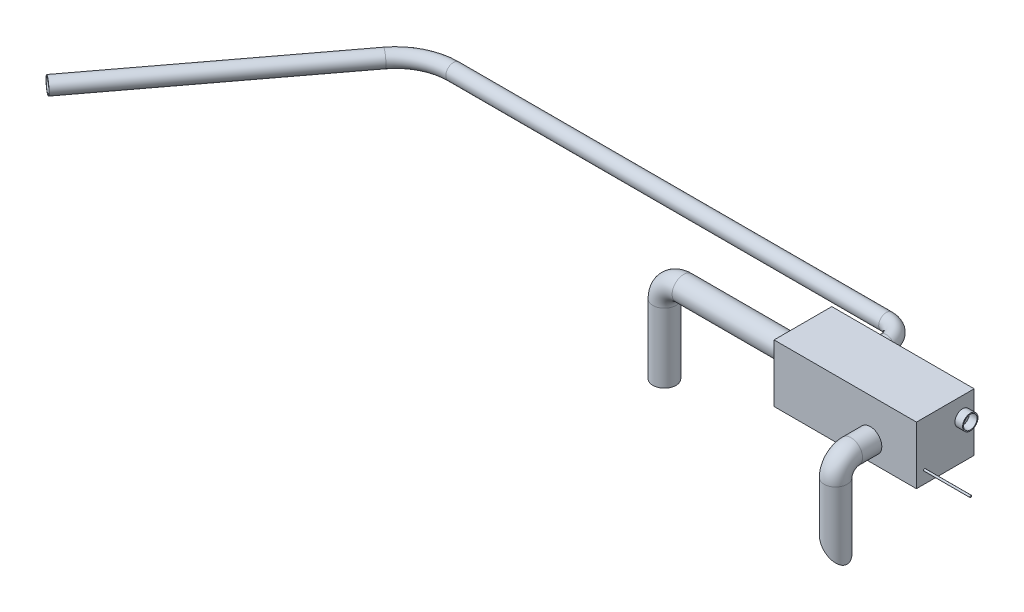
SolidWorks part; units mm, degrees
ref_plane "Front" through (0, 0, 0) normal (0, 0, 1) x (1, 0, 0)
ref_plane "Top" through (0, 0, 0) normal (0, 1, 0) x (1, 0, 0)
ref_plane "Right" through (0, 0, 0) normal (1, 0, 0) x (0, 0, -1)
sketch "Sketch1" plane through (0, 0, 0) normal (0, 1, 0) x (1, 0, 0)
  line L1 (-469.9, 190.5) -> (469.9, 190.5)
  line L2 (-469.9, 190.5) -> (-469.9, -190.5)
  line L3 (-469.9, -190.5) -> (469.9, -190.5)
  line L4 (469.9, 190.5) -> (469.9, -190.5)
  line L5 (-469.9, 190.5) -> (469.9, -190.5) construction
  line L6 (-469.9, -190.5) -> (469.9, 190.5) construction
  point P0 (0, 0)
  dimension "D1" = 381
  dimension "D2" = 939.8
extrude "Boss-Extrude1" add sketch "Sketch1" along normal blind 381
sketch "Sketch2" plane through (0, 0, 190.5) normal (0, 0, 1) x (1, 0, 0)
  line L0 (469.9, 381) -> (469.9, 0) construction
  line L1 (-469.9, 381) -> (469.9, 381) construction
  circle A0 centre (165.1, 127) radius 76.2
  circle A1 centre (165.1, 127) radius 69.85
  dimension "D1" = 152.4
  dimension "D3" = 254
  dimension "D4" = 139.7
  dimension "D2" = 304.8
extrude "Boss-Extrude2" add sketch "Sketch2" along normal blind 101.6
sketch "Sketch3" plane through (469.9, 0, 0) normal (1, 0, 0) x (0, 0, -1)
  line L0 (-190.5, 381) -> (190.5, 381) construction
  line L1 (190.5, 381) -> (190.5, 0) construction
  circle A0 centre (114.3, 254) radius 50.8
  circle A1 centre (114.3, 254) radius 44.45
  dimension "D1" = 101.6
  dimension "D2" = 88.9
  dimension "D3" = 127
  dimension "D4" = 76.2
extrude "Boss-Extrude3" add sketch "Sketch3" along normal blind 50.8
sketch "Sketch4" plane through (469.9, 0, 0) normal (1, 0, 0) x (0, 0, -1)
  circle A0 centre (-136.8501, 81.3511) radius 6.35
  dimension "D1" = 12.7
extrude "Boss-Extrude4" add sketch "Sketch4" along normal blind 304.8
sketch "Sketch5" plane through (0, 0, -190.5) normal (0, 0, -1) x (-1, 0, 0)
  line L0 (-469.9, 381) -> (469.9, 381) construction
  line L1 (469.9, 381) -> (469.9, 0) construction
  circle A0 centre (185.6926, 273.8882) radius 50.8
  circle A1 centre (185.6926, 273.8882) radius 44.45
  dimension "D1" = 101.6
  dimension "D2" = 88.9
  dimension "D4" = 284.2074
  dimension "D3" = 107.1118
extrude "Boss-Extrude5" add sketch "Sketch5" along normal blind 50.8
sketch "Sketch6" plane through (-469.9, 0, 0) normal (-1, 0, 0) x (0, 0, 1)
  line L0 (-190.5, 381) -> (190.5, 0) construction
  circle A0 centre (0, 190.5) radius 76.2
  circle A1 centre (0, 190.5) radius 69.85
  dimension "D1" = 152.4
  dimension "D2" = 139.7
extrude "Boss-Extrude6" add sketch "Sketch6" along normal blind 762
sketch "Sketch7" plane through (0, 0, 292.1) normal (0, 0, 1) x (1, 0, 0)
  circle A0 centre (165.1, 127) radius 76.2 construction
  circle A1 centre (165.1, 127) radius 76.2
  circle A2 centre (165.1, 127) radius 69.85 construction
  circle A3 centre (165.1, 127) radius 69.85
ref_point "Point1"
ref_plane "Plane1" through (165.1, 0, 0) normal (1, 0, 0) x (0, 0, -1)
sketch "Sketch8" plane through (165.1, 0, 0) normal (1, 0, 0) x (0, 0, -1)
  line L0 (-292.1, 127) -> (-317.5, 127)
  line L1 (-292.1, 203.2) -> (-292.1, 50.8) construction
  line L2 (-419.1, 25.4) -> (-419.1, -431.8)
  arc A0 (-317.5, 127) -> (-419.1, 25.4) centre (-317.5, 25.4) ccw
  dimension "D3" = 101.6
  dimension "D1" = 457.2
  dimension "D2" = 25.4
sweep "Sweep1" add profiles "Sketch7" path "Sketch8"
ref_point "Point2"
ref_plane "Plane2" through (0, 190.5, 0) normal (0, 1, 0) x (1, 0, 0)
sketch "Sketch9" plane through (0, 190.5, 0) normal (0, 1, 0) x (1, 0, 0)
  line L0 (-1231.9, 0) -> (-4279.9, 0)
  line L1 (-1231.9, 76.2) -> (-1231.9, -76.2) construction
  dimension "D1" = 3048
sketch "Sketch10" plane through (-1231.9, 0, 0) normal (-1, 0, 0) x (0, 0, 1)
  circle A0 centre (0, 190.5) radius 76.2 construction
  circle A1 centre (0, 190.5) radius 76.2
  circle A2 centre (0, 190.5) radius 69.85 construction
  circle A3 centre (0, 190.5) radius 69.85
sweep "Sweep2" [suppressed] add profiles "Sketch10" path "Sketch9"
ref_point "Point5"
ref_plane "Plane5" through (0, 273.8882, 0) normal (0, 1, 0) x (1, 0, 0)
sketch "Sketch13" plane through (0, 273.8882, 0) normal (0, 1, 0) x (1, 0, 0)
  line L0 (-185.6926, 241.3) -> (-185.6926, 266.7)
  line L1 (-134.8926, 241.3) -> (-236.4926, 241.3) construction
  line L2 (-181.0972, 292.7619) -> (330.9506, 1699.6019)
  line L3 (340.1415, 1751.7257) -> (340.1415, 2867.8535)
  line L4 (469.9, 190.5) -> (-469.9, 190.5) construction
  arc A0 (-185.6926, 266.7) -> (-181.0972, 292.7619) centre (-109.4926, 266.7) cw
  arc A1 (340.1415, 1751.7257) -> (330.9506, 1699.6019) centre (187.7415, 1751.7257) cw
  point P13 (340.1415, 1724.8535)
  dimension "D1" = 76.2
  dimension "D6" = 152.4
  dimension "D2" = 25.4
  dimension "D3" = 1524
  dimension "D4" = 1143
  dimension "D5" = 70
sketch "Sketch14" plane through (0, 0, -241.3) normal (0, 0, -1) x (-1, 0, 0)
  circle A0 centre (185.6926, 273.8882) radius 44.45 construction
  circle A1 centre (185.6926, 273.8882) radius 50.8
  circle A2 centre (185.6926, 273.8882) radius 50.8
  circle A3 centre (185.6926, 273.8882) radius 44.45
  dimension "D1" = 0
sweep "Sweep5" [suppressed] add profiles "Sketch14" path "Sketch13"
sketch "Sketch15" plane through (0, 273.8882, 0) normal (0, 1, 0) x (1, 0, 0)
  line L0 (-185.6926, 241.3) -> (-185.6926, 317.5)
  line L1 (-134.8926, 241.3) -> (-236.4926, 241.3) construction
  line L4 (2989.3074, 444.5) -> (-58.6926, 444.5)
  arc A0 (-185.6926, 317.5) -> (-58.6926, 444.5) centre (-58.6926, 317.5) cw
  dimension "D2" = 127
  dimension "D1" = 76.2
  dimension "D5" = 3048
sketch "Sketch16" plane through (0, 0, -241.3) normal (0, 0, -1) x (-1, 0, 0)
  circle A0 centre (185.6926, 273.8882) radius 44.45 construction
  circle A1 centre (185.6926, 273.8882) radius 50.8
  circle A2 centre (185.6926, 273.8882) radius 50.8
  circle A3 centre (185.6926, 273.8882) radius 44.45
  dimension "D1" = 0
sweep "Sweep6" [suppressed] add profiles "Sketch16" path "Sketch15"
sketch "Sketch22" plane through (0, 0, 190.5) normal (0, 0, 1) x (1, 0, 0)
  line L0 (88.9, -279.4) -> (241.3, -431.8)
  line L1 (88.9, 25.4) -> (88.9, -431.8) construction
  line L2 (241.3, -431.8) -> (88.9, -431.8)
  line L3 (88.9, -431.8) -> (88.9, -279.4)
  dimension "D1" = 45
extrude "Cut-Extrude3" cut sketch "Sketch22" along normal through all
sketch "Sketch23" [suppressed] plane through (2989.3074, 0, 0) normal (1, 0, 0) x (0, 0, -1)
  circle A0 centre (444.5, 273.8882) radius 44.45 construction
  circle A1 centre (444.5, 273.8882) radius 50.8
  circle A2 centre (444.5, 273.8882) radius 50.8
  circle A3 centre (444.5, 273.8882) radius 44.45
  dimension "D1" = 0
sketch "Sketch24" [suppressed] plane through (0, 190.5, 0) normal (0, 1, 0) x (1, 0, 0)
  line L0 (2989.3074, 444.5) -> (2735.3074, 444.5)
  line L1 (2989.3074, 393.7) -> (2989.3074, 495.3) construction
  line L2 (2481.3074, 376.4409) -> (2041.3664, 122.4409)
  arc A0 (2735.3074, 444.5) -> (2481.3074, 376.4409) centre (2735.3074, -63.5) ccw
  dimension "D1" = 508
  dimension "D2" = 254
  dimension "D3" = 150
  dimension "D4" = 508
sweep "Sweep7" [suppressed] add profiles "Sketch23" path "Sketch24"
sketch "Sketch25" [suppressed] plane through (-3771.9, 0, 0) normal (-1, 0, 0) x (0, 0, 1)
  circle A0 centre (0, 190.5) radius 69.85 construction
  circle A1 centre (0, 190.5) radius 76.2
  circle A2 centre (0, 190.5) radius 76.2
  circle A3 centre (0, 190.5) radius 69.85
  dimension "D1" = 0
ref_plane "Plane6" through (0, 0, 0) normal (0, 0, 1) x (1, 0, 0)
sketch "Sketch26" plane through (0, 0, 0) normal (0, 0, 1) x (1, 0, 0)
  line L0 (-1231.9, 190.5) -> (-1257.3, 190.5)
  line L1 (-1231.9, 266.7) -> (-1231.9, 114.3) construction
  line L2 (-1384.3, 63.5) -> (-1384.3, -393.7)
  arc A0 (-1257.3, 190.5) -> (-1384.3, 63.5) centre (-1257.3, 63.5) ccw
  dimension "D1" = 127
  dimension "D2" = 25.4
  dimension "D3" = 457.2
sketch "Sketch27" plane through (-1231.9, 0, 0) normal (-1, 0, 0) x (0, 0, 1)
  circle A0 centre (0, 190.5) radius 76.2 construction
  circle A1 centre (0, 190.5) radius 76.2
  circle A3 centre (0, 190.5) radius 69.85 construction
  circle A4 centre (0, 190.5) radius 69.85
sweep "Sweep8" add profiles "Sketch27" path "Sketch26"
sketch "Sketch28" plane through (0, 273.8882, 0) normal (0, 1, 0) x (1, 0, 0)
  line L0 (-185.6926, 241.3) -> (-185.6926, 266.7)
  line L1 (-134.8926, 241.3) -> (-236.4926, 241.3) construction
  line L2 (-312.6926, 393.7) -> (-3170.7331, 393.7)
  line L3 (-3475.0132, 241.9915) -> (-4430.7198, -1026.2739)
  arc A0 (-185.6926, 266.7) -> (-312.6926, 393.7) centre (-312.6926, 266.7) ccw
  arc A1 (-3170.7331, 393.7) -> (-3475.0132, 241.9915) centre (-3170.7331, 12.7) ccw
  point P10 (-3360.6926, 393.7)
  dimension "D1" = 127
  dimension "D6" = 381
  dimension "D2" = 3048
  dimension "D3" = 25.4
  dimension "D4" = 127
  dimension "D5" = 1778
sketch "Sketch29" plane through (0, 0, -241.3) normal (0, 0, -1) x (-1, 0, 0)
  circle A0 centre (185.6926, 273.8882) radius 44.45 construction
  circle A1 centre (185.6926, 273.8882) radius 50.8
  circle A2 centre (185.6926, 273.8882) radius 50.8
  circle A3 centre (185.6926, 273.8882) radius 44.45
  dimension "D1" = 0
sweep "Sweep9" add profiles "Sketch29" path "Sketch28"
